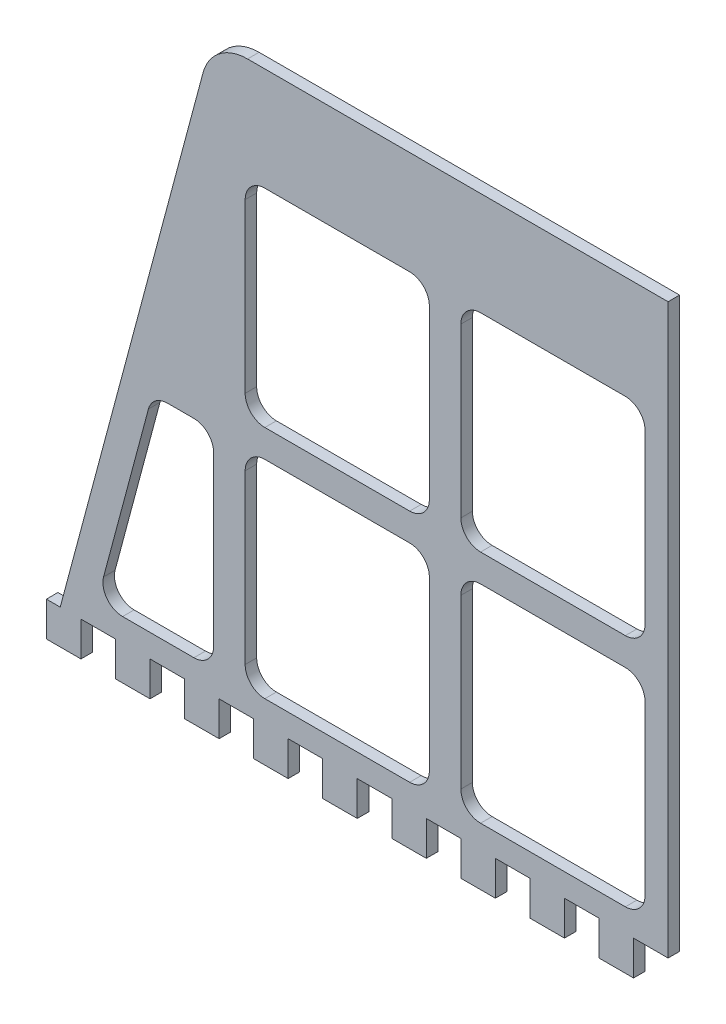
SolidWorks part; units mm, degrees
material "Balsa"
ref_plane "Front Plane" through (0, 0, 0) normal (0, 0, 1) x (1, 0, 0)
ref_plane "Top Plane" through (0, 0, 0) normal (0, 1, 0) x (1, 0, 0)
ref_plane "Right Plane" through (0, 0, 0) normal (1, 0, 0) x (0, 0, -1)
sketch "Sketch1" plane through (0, 0, 0) normal (0, 0, 1) x (1, 0, 0)
  line L0 (0, 0) -> (335.28, 0)
  line L1 (335.28, 0) -> (335.28, 313.5173)
  line L2 (335.28, 313.5173) -> (103.3213, 313.5173)
  line L3 (78.7832, 294.6776) -> (0, 0)
  arc A0 (103.3213, 313.5173) -> (78.7832, 294.6776) centre (103.3213, 288.1173) ccw
  point P8 (83.82, 313.5173)
  point P11 (335.28, 313.5173)
  dimension "D4" = 25.4
  dimension "D1" = 335.28
  dimension "D2" = 313.5173
  dimension "D3" = 251.46
extrude "Boss-Extrude1" add sketch "Sketch1" along normal blind 6.35
sketch "Sketch2" plane through (0, 0, 6.35) normal (0, 0, 1) x (1, 0, 0)
  line L0 (335.28, 0) -> (335.28, 313.5173) construction
  line L1 (311.7054, 12.7) -> (231.8546, 12.7)
  line L2 (322.58, 23.5746) -> (322.58, 116.1254)
  line L3 (311.7054, 127) -> (231.8546, 127)
  line L4 (220.98, 23.5746) -> (220.98, 116.1254)
  line L5 (0, 0) -> (335.28, 0) construction
  line L6 (203.6033, 23.5746) -> (203.6033, 116.1254)
  line L7 (192.7288, 12.7) -> (112.8779, 12.7)
  line L8 (102.0033, 23.5746) -> (102.0033, 116.1254)
  line L9 (192.7288, 127) -> (112.8779, 127)
  line L10 (84.6266, 23.5746) -> (84.6266, 116.1254)
  line L11 (73.7521, 12.7) -> (34.4142, 12.7)
  line L13 (73.7521, 127) -> (59.158, 127)
  line L14 (203.6033, 153.1146) -> (203.6033, 245.6654)
  line L15 (192.7288, 142.24) -> (112.8779, 142.24)
  line L16 (102.0033, 153.1146) -> (102.0033, 245.6654)
  line L17 (192.7288, 256.54) -> (112.8779, 256.54)
  line L18 (84.6266, 153.1146) -> (84.6266, 251.1027)
  line L19 (73.7521, 142.24) -> (69.0472, 142.24)
  line L30 (322.58, 153.1146) -> (322.58, 245.6654)
  line L31 (311.7054, 142.24) -> (231.8546, 142.24)
  line L32 (220.98, 153.1146) -> (220.98, 245.6654)
  line L33 (311.7054, 256.54) -> (231.8546, 256.54)
  line L38 (84.6266, 253.4908) -> (58.5416, 155.9233)
  line L40 (78.7832, 294.6776) -> (0, 0) construction
  line L41 (-16.9734, 12.7) -> (-16.9734, 127) [skipped]
  line L42 (-16.9734, 136.8027) -> (-16.9734, 251.1027) [skipped]
  line L43 (84.6266, 256.54) -> (-16.9734, 256.54) [skipped]
  line L44 (48.6524, 118.9342) -> (23.9086, 26.3833)
  line L45 (84.6266, 271.78) -> (84.6266, 386.08) [skipped]
  line L46 (84.6266, 386.08) -> (-16.9734, 386.08) [skipped]
  line L47 (-16.9734, 271.78) -> (-16.9734, 386.08) [skipped]
  line L48 (84.6266, 271.78) -> (-16.9734, 271.78) [skipped]
  line L49 (203.6033, 271.78) -> (203.6033, 386.08) [skipped]
  line L50 (203.6033, 386.08) -> (102.0033, 386.08) [skipped]
  line L51 (102.0033, 271.78) -> (102.0033, 386.08) [skipped]
  line L52 (203.6033, 271.78) -> (102.0033, 271.78) [skipped]
  line L53 (322.58, 271.78) -> (322.58, 386.08) [skipped]
  line L54 (322.58, 386.08) -> (220.98, 386.08) [skipped]
  line L55 (220.98, 271.78) -> (220.98, 386.08) [skipped]
  line L56 (322.58, 271.78) -> (220.98, 271.78) [skipped]
  arc A0 (69.0472, 142.24) -> (58.5416, 155.9233) centre (69.0472, 153.1146) cw
  arc A1 (84.6266, 153.1146) -> (73.7521, 142.24) centre (73.7521, 153.1146) cw
  arc A2 (84.6266, 23.5746) -> (73.7521, 12.7) centre (73.7521, 23.5746) cw
  arc A3 (34.4142, 12.7) -> (23.9086, 26.3833) centre (34.4142, 23.5746) cw
  arc A4 (59.158, 127) -> (48.6524, 118.9342) centre (59.158, 116.1254) ccw
  arc A5 (84.6266, 116.1254) -> (73.7521, 127) centre (73.7521, 116.1254) ccw
  arc A6 (102.0033, 116.1254) -> (112.8779, 127) centre (112.8779, 116.1254) cw
  arc A7 (112.8779, 12.7) -> (102.0033, 23.5746) centre (112.8779, 23.5746) cw
  arc A8 (203.6033, 23.5746) -> (192.7288, 12.7) centre (192.7288, 23.5746) cw
  arc A9 (203.6033, 116.1254) -> (192.7288, 127) centre (192.7288, 116.1254) ccw
  arc A10 (231.8546, 127) -> (220.98, 116.1254) centre (231.8546, 116.1254) ccw
  arc A11 (231.8546, 12.7) -> (220.98, 23.5746) centre (231.8546, 23.5746) cw
  arc A12 (311.7054, 12.7) -> (322.58, 23.5746) centre (311.7054, 23.5746) ccw
  arc A13 (322.58, 116.1254) -> (311.7054, 127) centre (311.7054, 116.1254) ccw
  arc A14 (322.58, 153.1146) -> (311.7054, 142.24) centre (311.7054, 153.1146) cw
  arc A15 (322.58, 245.6654) -> (311.7054, 256.54) centre (311.7054, 245.6654) ccw
  arc A16 (220.98, 245.6654) -> (231.8546, 256.54) centre (231.8546, 245.6654) cw
  arc A17 (231.8546, 142.24) -> (220.98, 153.1146) centre (231.8546, 153.1146) cw
  arc A18 (112.8779, 142.24) -> (102.0033, 153.1146) centre (112.8779, 153.1146) cw
  arc A19 (203.6033, 153.1146) -> (192.7288, 142.24) centre (192.7288, 153.1146) cw
  arc A20 (203.6033, 245.6654) -> (192.7288, 256.54) centre (192.7288, 245.6654) ccw
  arc A21 (102.0033, 245.6654) -> (112.8779, 256.54) centre (112.8779, 245.6654) cw
  point P33 (50.8088, 127)
  point P83 (220.98, 127)
  point P86 (220.98, 12.7)
  point P91 (322.58, 127)
  dimension "D7" = 10.8746
  dimension "D1" = 114.3
  dimension "D2" = 101.6
  dimension "D3" = 12.7
  dimension "D4" = 12.7
  dimension "D5" = 3
  dimension "D6" = 3
extrude "Cut-Extrude1" cut sketch "Sketch2" along direction (0, 0, 1) on the side against the normal up to surface (6.35 mm away) contours L18 L38 L19 | L14 L17 L16 L15 | L13 L44 L11 L10 | L6 L9 L8 L7 | L4 L1 L2 L3 | L30 L33 L32 L31 region at (271.78, 69.85, 6.35) region at (152.8033, 69.85, 6.35) region at (59.3813, 64.1169, 6.35) region at (152.8033, 199.39, 6.35) region at (271.78, 199.39, 6.35) up to face at (169.8931, 185.1758, 0)
sketch "Sketch3" plane through (0, 0, 6.35) normal (0, 0, 1) x (1, 0, 0)
  line L0 (316.23, 0) -> (316.23, -19.05)
  line L1 (335.28, 0) -> (316.23, 0)
  line L2 (335.28, 0) -> (335.28, -19.05)
  line L3 (335.28, -19.05) -> (316.23, -19.05)
  line L4 (316.23, 0) -> (316.23, -19.05)
  line L5 (316.23, 0) -> (297.18, 0)
  line L6 (297.18, 0) -> (297.18, -19.05)
  line L7 (316.23, -19.05) -> (297.18, -19.05)
  line L8 (297.18, 0) -> (297.18, -19.05)
  line L9 (297.18, 0) -> (278.13, 0)
  line L10 (278.13, 0) -> (278.13, -19.05)
  line L11 (297.18, -19.05) -> (278.13, -19.05)
  line L12 (278.13, 0) -> (278.13, -19.05)
  line L13 (278.13, 0) -> (259.08, 0)
  line L14 (259.08, 0) -> (259.08, -19.05)
  line L15 (278.13, -19.05) -> (259.08, -19.05)
  line L16 (259.08, 0) -> (259.08, -19.05)
  line L17 (259.08, 0) -> (240.03, 0)
  line L18 (240.03, 0) -> (240.03, -19.05)
  line L19 (259.08, -19.05) -> (240.03, -19.05)
  line L20 (240.03, 0) -> (240.03, -19.05)
  line L21 (240.03, 0) -> (220.98, 0)
  line L22 (220.98, 0) -> (220.98, -19.05)
  line L23 (240.03, -19.05) -> (220.98, -19.05)
  line L24 (220.98, 0) -> (220.98, -19.05)
  line L25 (220.98, 0) -> (201.93, 0)
  line L26 (201.93, 0) -> (201.93, -19.05)
  line L27 (220.98, -19.05) -> (201.93, -19.05)
  line L28 (201.93, 0) -> (201.93, -19.05)
  line L29 (201.93, 0) -> (182.88, 0)
  line L30 (182.88, 0) -> (182.88, -19.05)
  line L31 (201.93, -19.05) -> (182.88, -19.05)
  line L32 (182.88, 0) -> (182.88, -19.05)
  line L33 (182.88, 0) -> (163.83, 0)
  line L34 (163.83, 0) -> (163.83, -19.05)
  line L35 (182.88, -19.05) -> (163.83, -19.05)
  line L36 (163.83, 0) -> (163.83, -19.05)
  line L37 (163.83, 0) -> (144.78, 0)
  line L38 (144.78, 0) -> (144.78, -19.05)
  line L39 (163.83, -19.05) -> (144.78, -19.05)
  line L40 (144.78, 0) -> (144.78, -19.05)
  line L41 (144.78, 0) -> (125.73, 0)
  line L42 (125.73, 0) -> (125.73, -19.05)
  line L43 (144.78, -19.05) -> (125.73, -19.05)
  line L44 (125.73, 0) -> (125.73, -19.05)
  line L45 (125.73, 0) -> (106.68, 0)
  line L46 (106.68, 0) -> (106.68, -19.05)
  line L47 (125.73, -19.05) -> (106.68, -19.05)
  line L48 (106.68, 0) -> (106.68, -19.05)
  line L49 (106.68, 0) -> (87.63, 0)
  line L50 (87.63, 0) -> (87.63, -19.05)
  line L51 (106.68, -19.05) -> (87.63, -19.05)
  line L52 (87.63, 0) -> (87.63, -19.05)
  line L53 (87.63, 0) -> (68.58, 0)
  line L54 (68.58, 0) -> (68.58, -19.05)
  line L55 (87.63, -19.05) -> (68.58, -19.05)
  line L56 (68.58, 0) -> (68.58, -19.05)
  line L57 (68.58, 0) -> (49.53, 0)
  line L58 (49.53, 0) -> (49.53, -19.05)
  line L59 (68.58, -19.05) -> (49.53, -19.05)
  line L60 (49.53, 0) -> (49.53, -19.05)
  line L61 (49.53, 0) -> (30.48, 0)
  line L62 (30.48, 0) -> (30.48, -19.05)
  line L63 (49.53, -19.05) -> (30.48, -19.05)
  line L64 (30.48, 0) -> (30.48, -19.05)
  line L65 (30.48, 0) -> (11.43, 0)
  line L66 (11.43, 0) -> (11.43, -19.05)
  line L67 (30.48, -19.05) -> (11.43, -19.05)
  line L68 (11.43, 0) -> (11.43, -19.05)
  line L69 (11.43, 0) -> (-7.62, 0)
  line L70 (-7.62, 0) -> (-7.62, -19.05)
  line L71 (11.43, -19.05) -> (-7.62, -19.05)
  line M22 (0, 0) -> (335.28, 0)
  dimension "D1" = 19.05
  dimension "D2" = 19.05
  dimension "D3" = 18
extrude "Boss-Extrude2" add sketch "Sketch3" against normal up to surface (6.35 mm away) contours L71 L66 L69 L70 M22 | L63 L58 L62 M22 | L55 L50 L54 M22 | L47 L42 L46 M22 | L39 L34 L38 M22 | L31 L26 L30 M22 | L23 L18 L22 M22 | L15 L10 L14 M22 | L7 L0 L6 M22 region at (306.705, -9.525, 6.35) region at (268.605, -9.525, 6.35) region at (230.505, -9.525, 6.35) region at (192.405, -9.525, 6.35) region at (154.305, -9.525, 6.35) region at (116.205, -9.525, 6.35) region at (78.105, -9.525, 6.35) region at (40.005, -9.525, 6.35) region at (1.905, -9.525, 6.35) up to face at (271.78, 199.39, 0)
